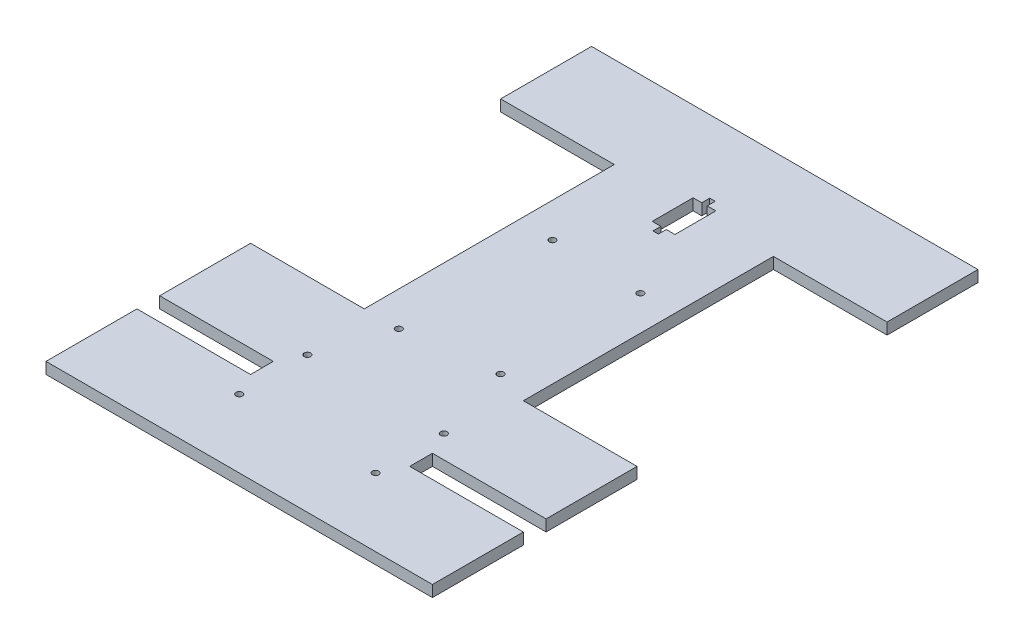
SolidWorks part; units mm, degrees
ref_plane "Front Plane" through (0, 0, 0) normal (0, 0, 1) x (1, 0, 0)
ref_plane "Top Plane" through (0, 0, 0) normal (0, 1, 0) x (1, 0, 0)
ref_plane "Right Plane" through (0, 0, 0) normal (1, 0, 0) x (0, 0, -1)
sketch "Sketch1" plane through (0, 0, 0) normal (0, 1, 0) x (1, 0, 0)
  line L0 (0, 152.4) -> (0, -152.4) construction
  line L1 (-44.45, 152.4) -> (44.45, 152.4)
  line L2 (-44.45, 152.4) -> (-44.45, -152.4)
  line L3 (-44.45, -152.4) -> (44.45, -152.4)
  line L4 (44.45, 152.4) -> (44.45, -152.4)
  line L5 (-44.45, 152.4) -> (44.45, -152.4) construction
  line L6 (-44.45, -152.4) -> (44.45, 152.4) construction
  line L7 (-107.95, 101.6) -> (-44.45, 101.6)
  line L8 (-107.95, 101.6) -> (-107.95, 152.4)
  line L9 (-107.95, 152.4) -> (-44.45, 152.4)
  line L10 (-44.45, 101.6) -> (-44.45, 152.4)
  line L11 (-107.95, 101.6) -> (-44.45, 152.4) construction
  line L12 (-107.95, 152.4) -> (-44.45, 101.6) construction
  line L13 (107.95, -152.4) -> (44.45, -152.4)
  line L14 (-107.95, -101.6) -> (-44.45, -101.6)
  line L15 (-107.95, -101.6) -> (-107.95, -152.4)
  line L16 (-107.95, -152.4) -> (-44.45, -152.4)
  line L17 (-44.45, -101.6) -> (-44.45, -152.4)
  line L18 (-107.95, -101.6) -> (-44.45, -152.4) construction
  line L19 (-107.95, -152.4) -> (-44.45, -101.6) construction
  line L20 (-107.95, -38.1) -> (-44.45, -38.1)
  line L21 (-107.95, -38.1) -> (-107.95, -88.9)
  line L22 (-107.95, -88.9) -> (-44.45, -88.9)
  line L23 (-44.45, -38.1) -> (-44.45, -88.9)
  line L24 (-107.95, -38.1) -> (-44.45, -88.9) construction
  line L25 (-107.95, -88.9) -> (-44.45, -38.1) construction
  line L26 (44.45, -101.6) -> (44.45, -152.4)
  line L27 (107.95, -101.6) -> (44.45, -101.6)
  line L28 (107.95, -101.6) -> (107.95, -152.4)
  line L29 (107.95, -88.9) -> (44.45, -88.9)
  line L30 (44.45, -38.1) -> (44.45, -88.9)
  line L31 (107.95, -38.1) -> (44.45, -38.1)
  line L32 (107.95, -38.1) -> (107.95, -88.9)
  line L33 (107.95, 152.4) -> (44.45, 152.4)
  line L34 (44.45, 101.6) -> (44.45, 152.4)
  line L35 (107.95, 101.6) -> (44.45, 101.6)
  line L36 (107.95, 101.6) -> (107.95, 152.4)
  point P0 (0, 0)
  point P6 (-76.2, 127)
  point P12 (-76.2, -127)
  point P13 (-76.2, -63.5)
  dimension "D1" = 304.8
  dimension "D2" = 88.9
  dimension "D3" = 50.8
  dimension "D4" = 63.5
  dimension "D5" = 12.7
extrude "Boss-Extrude1" add sketch "Sketch1" along normal blind 6.35 contours L9 L8 L7 L2 | L4 L1 L2 L3 | L35 L36 L33 L4 | L32 L31 L4 L29 | L28 L27 L4 L13 | L15 L16 L2 L14 | L21 L22 L2 L20 region at (0, 0, 0) region at (-76.2, 0, -127) region at (76.2, 0, -127) region at (-76.2, 0, 63.5) region at (76.2, 0, 63.5) region at (-76.2, 0, 127) region at (76.2, 0, 127)
sketch "Sketch2" plane through (0, 6.35, 0) normal (0, 1, 0) x (1, 0, 0)
  line L0 (-44.45, -88.9) -> (-44.45, -101.6) construction
  line L3 (-44.45, 47.7291) -> (-26.9545, 47.7291) construction
  line L4 (-44.45, 101.6) -> (-44.45, -38.1) construction
  line L5 (26.9545, 46.5861) -> (44.45, 46.5861) construction
  line L6 (44.45, 101.6) -> (44.45, -38.1) construction
  line L8 (-6.35, 84.6861) -> (6.35, 84.6861)
  line L9 (-6.35, 84.6861) -> (-6.35, 107.5461)
  line L10 (-6.35, 107.5461) -> (6.35, 107.5461)
  line L11 (6.35, 84.6861) -> (6.35, 107.5461)
  line L12 (-6.35, 84.6861) -> (6.35, 107.5461) construction
  line L13 (-6.35, 107.5461) -> (6.35, 84.6861) construction
  line L14 (-1.524, 80.2411) -> (1.524, 80.2411)
  line L15 (-1.524, 80.2411) -> (-1.524, 84.6861)
  line L16 (-1.524, 84.6861) -> (1.524, 84.6861)
  line L17 (1.524, 80.2411) -> (1.524, 84.6861)
  line L18 (-1.524, 80.2411) -> (1.524, 84.6861) construction
  line L19 (-1.524, 84.6861) -> (1.524, 80.2411) construction
  line L20 (-1.524, 111.9911) -> (1.524, 111.9911)
  line L21 (-1.524, 111.9911) -> (-1.524, 107.5461)
  line L22 (-1.524, 107.5461) -> (1.524, 107.5461)
  line L23 (1.524, 111.9911) -> (1.524, 107.5461)
  line L24 (-1.524, 111.9911) -> (1.524, 107.5461) construction
  line L25 (-1.524, 107.5461) -> (1.524, 111.9911) construction
  circle A0 centre (-38.1, -76.2) radius 1.8097
  circle A1 centre (38.1, -76.2) radius 1.8097
  circle A2 centre (-38.1, -114.3) radius 1.8097
  circle A3 centre (38.1, -114.3) radius 1.8097
  circle A4 centre (-25.1447, 47.7291) radius 1.8098
  circle A5 centre (25.1447, 46.5861) radius 1.8098
  circle A6 centre (25.1447, -31.5697) radius 1.8098
  circle A7 centre (-25.1447, -38.1) radius 1.8098
  point P17 (-44.45, -95.25)
  point P20 (0, 109.7686)
  point P25 (0, 96.1161)
  point P34 (0, 82.4636)
  point P43 (0, 0)
  dimension "D1" = 3.6195
  dimension "D2" = 38.1
  dimension "D3" = 76.2
  dimension "D8" = 50.2895
  dimension "D12" = 4.445
  dimension "D4" = 38.1
  dimension "D5" = 19.05
  dimension "D6" = 78.1558
  dimension "D7" = 85.8291
  dimension "D9" = 1.143
  dimension "D10" = 12.7
  dimension "D11" = 22.86
  dimension "D13" = 3.048
  dimension "D14" = 38.1
extrude "Cut-Extrude1" cut sketch "Sketch2" against normal through all contours A2 | A3 | A1 | A0 | L8 L11 L10 L9 | A7 | A6 | A5 | A4 | L14 L17 L16 L15 | L23 L22 L21 L20 region at (0, 6.35, -96.1161) region at (-38.1, 6.35, 76.2) region at (38.1, 6.35, 76.2) region at (-38.1, 6.35, 114.3) region at (38.1, 6.35, 114.3)
